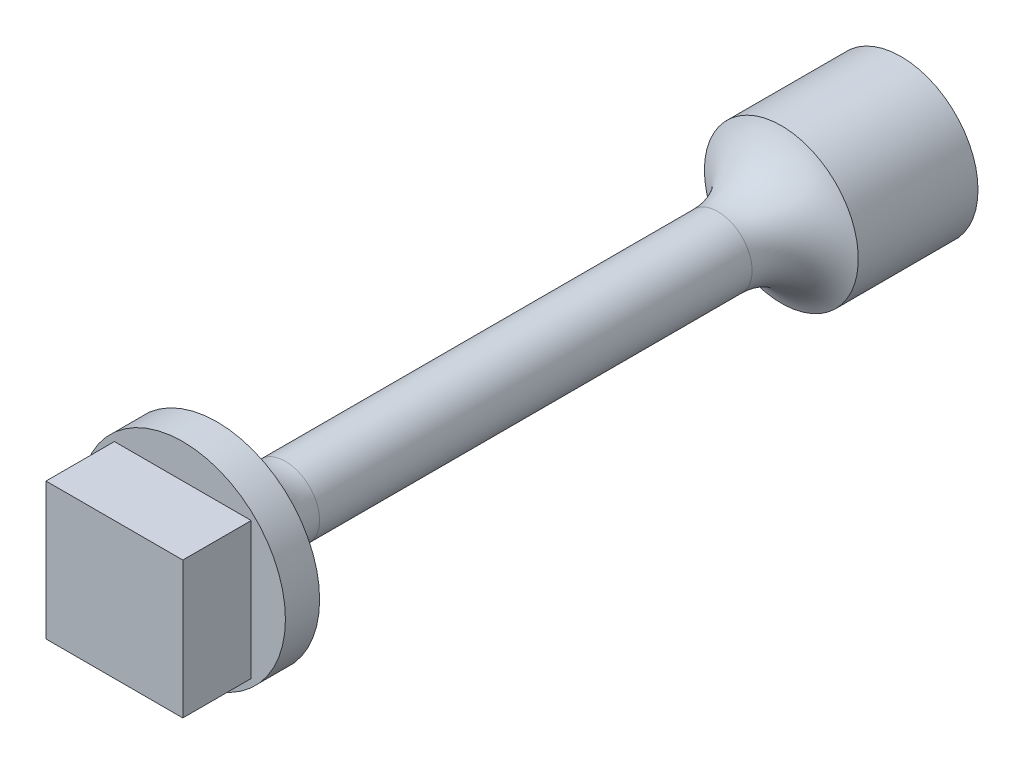
SolidWorks part; units mm, degrees
ref_plane "Front Plane" through (0, 0, 0) normal (0, 0, 1) x (1, 0, 0)
ref_plane "Top Plane" through (0, 0, 0) normal (0, 1, 0) x (1, 0, 0)
ref_plane "Right Plane" through (0, 0, 0) normal (1, 0, 0) x (0, 0, -1)
sketch "草图1" plane through (0, 0, 0) normal (0, 0, 1) x (1, 0, 0)
  circle A0 centre (0, 0) radius 2.25
  dimension "D1" = 4.5
extrude "凸台-拉伸2" add sketch "草图1" along normal blind 20
sketch "草图7" plane through (0, 0, 0) normal (0, 0, 1) x (1, 0, 0)
  line L1 (1.2, -1.2) -> (-1.2, -1.2)
  line L2 (1.2, -1.2) -> (1.2, 1.2)
  line L3 (1.2, 1.2) -> (-1.2, 1.2)
  line L4 (-1.2, -1.2) -> (-1.2, 1.2)
  line L5 (1.2, -1.2) -> (-1.2, 1.2) construction
  line L6 (1.2, 1.2) -> (-1.2, -1.2) construction
  point P0 (0, 0)
  dimension "D1" = 2.4
  dimension "D2" = 2.4
extrude "切除-拉伸3" cut sketch "草图7" along normal blind 2.5 from surface starting at face at (2.25, 0, 0)
sketch "草图9" plane through (0, 0, 20) normal (0, 0, 1) x (1, 0, 0)
  circle A0 centre (0, 0) radius 3
extrude "凸台-拉伸4" add sketch "草图9" along normal blind 1
sketch "草图10" plane through (0, 0, 21) normal (0, 0, 1) x (1, 0, 0)
  line L1 (2, -2) -> (-2, -2)
  line L2 (2, -2) -> (2, 2)
  line L3 (2, 2) -> (-2, 2)
  line L4 (-2, -2) -> (-2, 2)
  line L5 (2, -2) -> (-2, 2) construction
  line L6 (2, 2) -> (-2, -2) construction
  point P0 (0, 0)
  dimension "D1" = 4
  dimension "D2" = 4
extrude "凸台-拉伸5" add sketch "草图10" along normal blind 2
sketch "草图12" plane through (0, 0, 0) normal (0, 0, -1) x (-1, 0, 0)
  circle A0 centre (0, 0) radius 1
extrude "切除-拉伸4" cut sketch "草图12" along normal blind 16.5 from surface flip side to cut starting at face at (2.25, 0, 20)
fillet "圆角1" radius 2 2 edges at (1, 0, 3.5) (1, 0, 20)
